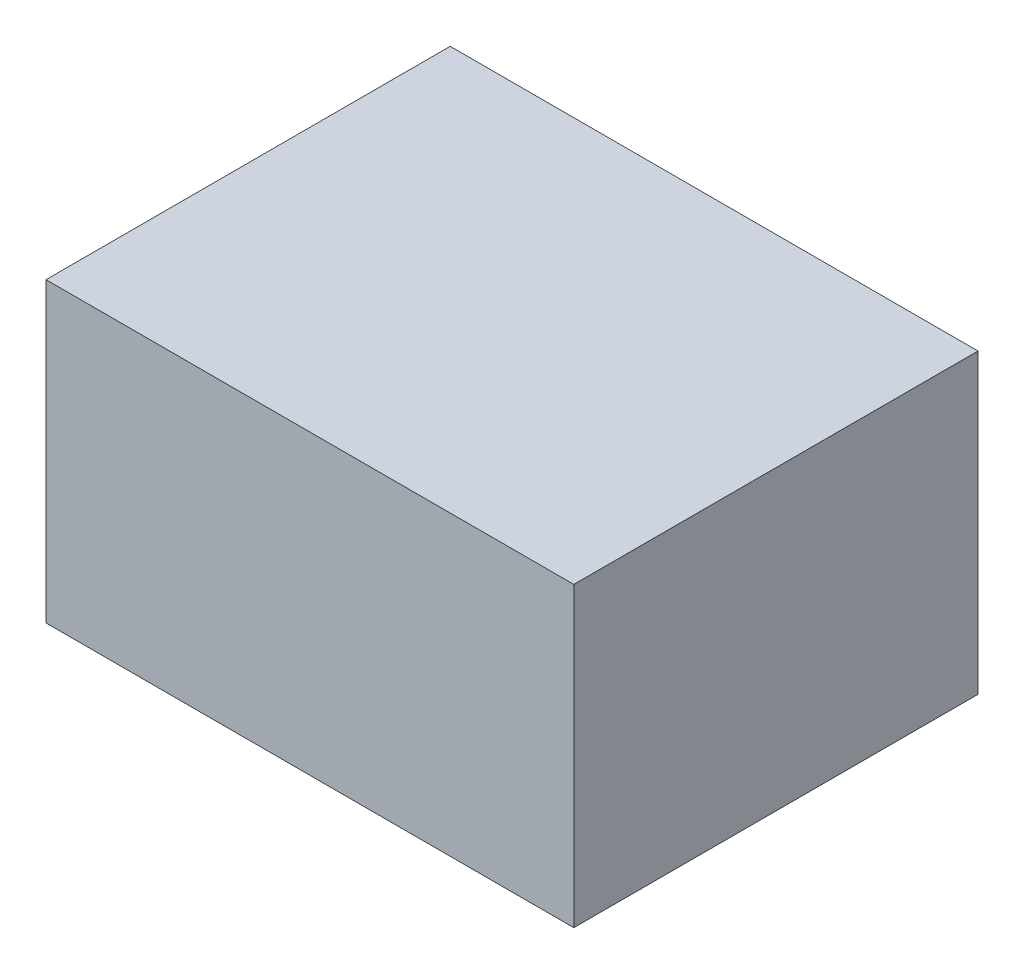
SolidWorks part; units mm, degrees
ref_plane "Front Plane" through (0, 0, 0) normal (0, 0, 1) x (1, 0, 0)
ref_plane "Top Plane" through (0, 0, 0) normal (0, 1, 0) x (1, 0, 0)
ref_plane "Right Plane" through (0, 0, 0) normal (1, 0, 0) x (0, 0, -1)
sketch "Sketch1" plane through (0, 0, 0) normal (0, 1, 0) x (1, 0, 0)
  line L1 (-158, -121) -> (158, -121)
  line L2 (-158, -121) -> (-158, 121)
  line L3 (-158, 121) -> (158, 121)
  line L4 (158, -121) -> (158, 121)
  line L5 (-158, -121) -> (158, 121) construction
  line L6 (-158, 121) -> (158, -121) construction
  point P0 (0, 0)
  dimension "D1" = 316
  dimension "D2" = 242
extrude "Boss-Extrude1" add sketch "Sketch1" along normal blind 178
equation "\"PCLength\"= 316mm'Length across I/O from PS to GPU"
equation "\"PCWidth\"= 242mm'Distance of longest part parallel to GPU(ussually GPU)"
equation "\"PCHeight\"= 178mm'Tallest point with mobo laying flat"
equation "\"WallThickness\"= 9mm'Thickness of each outer tank wall"
equation "\"ThermoBarrierThickness\"= 3mm'Thickness of barrier between hot side and cold side"
equation "\"HotSideGap\"= 25mm'Space in the hot side for a pump"
equation "\"PCClearance\"= 30mm'Clearance from top of tank to top of PC"
equation "\"RadiatorHeight\"= 275mm'Final Height from ground of radiators"
equation "\"D1@Sketch1\"=\"PCLength\""
equation "\"D2@Sketch1\"=\"PCWidth\""
equation "\"D1@Boss-Extrude1\"=\"PCHeight\""
